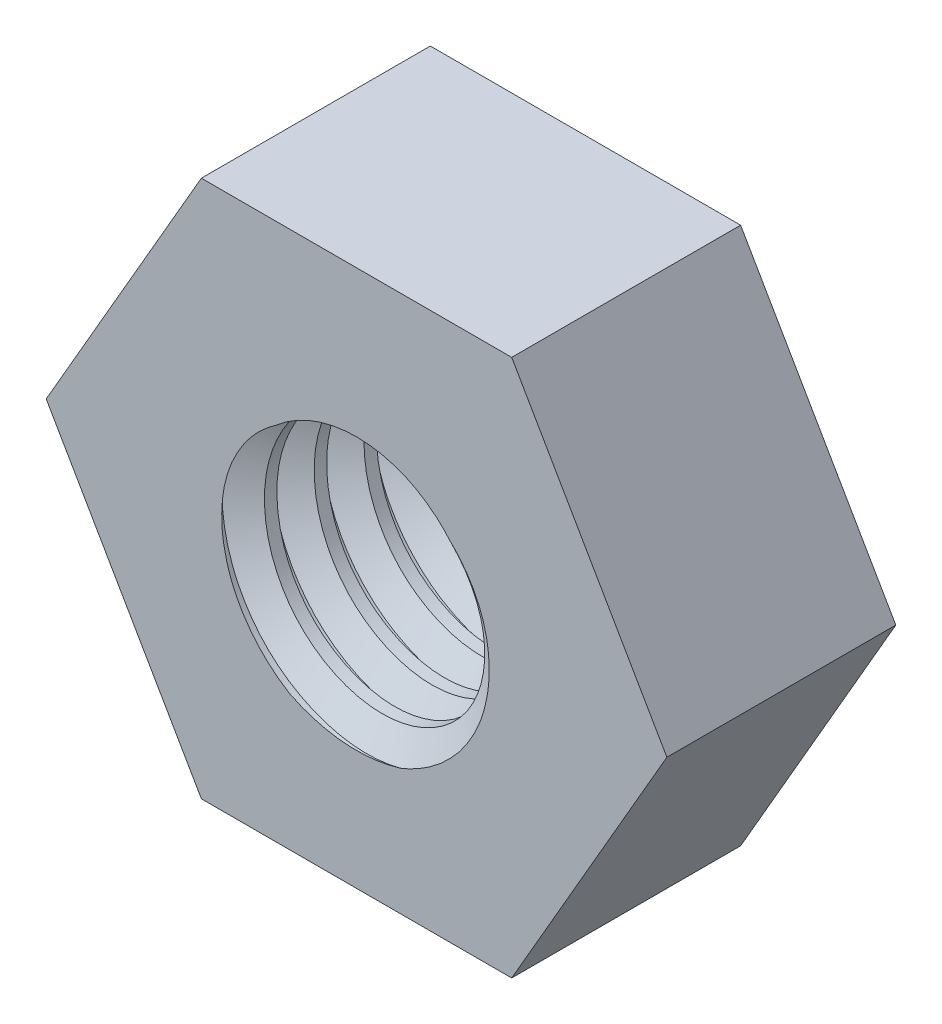
SolidWorks part; units mm, degrees
ref_plane "Plano frontal" through (0, 0, 0) normal (0, 0, 1) x (1, 0, 0)
ref_plane "Plano superior" through (0, 0, 0) normal (0, 1, 0) x (1, 0, 0)
ref_plane "Plano direito" through (0, 0, 0) normal (1, 0, 0) x (0, 0, -1)
sketch "Esboço1" plane through (0, 0, 0) normal (0, 0, 1) x (1, 0, 0)
  line L0 (3.1177, 0) -> (0, 0) construction
  line L1 (3.1177, 0) -> (1.5588, 2.7)
  line L2 (1.5588, 2.7) -> (-1.5588, 2.7)
  line L3 (-1.5588, 2.7) -> (-3.1177, 0)
  line L4 (-3.1177, 0) -> (-1.5588, -2.7)
  line L5 (-1.5588, -2.7) -> (1.5588, -2.7)
  line L6 (1.5588, -2.7) -> (3.1177, 0)
  circle A0 centre (0, 0) radius 2.7 construction
  circle A1 centre (0, 0) radius 1.5
  dimension "D1" = 5.4
  dimension "D2" = 3
extrude "Ressalto-extrusão1" add sketch "Esboço1" along normal blind 5 and the other way blind 5
thread "Rosca1" pitch 0.5 method extrude profile "Perfil da rosca2" start angle 0, offset 0, length 0, pitch 0.5, diameter 3
ref_plane "Plano2" through (-1.5, 0, 5) normal (0, -1, 0) x (-1, 0, 0)
sketch "Perfil da rosca2" plane through (-1.5, 0, 5) normal (0, -1, 0) x (-1, 0, 0)
  line L0 (0, 0) -> (0, 0.5) construction
  line L11 (0, 0) -> (0, 0.4375)
  line L12 (0, 0.4375) -> (-0.2706, 0.2812)
  line L13 (-0.2706, 0.2812) -> (-0.2706, 0.1562)
  line L15 (-0.2706, 0.1562) -> (0, 0)
  line L17 (-0.2706, 0.2187) -> (0, 0.2187) construction
  point P2 (0, 0)
  dimension "Pitch" = 0.5
  dimension "Profile_Angle" = 60
  dimension "Profile_Land" = 0.125
  dimension "Profile_Height" = 0.2706
sketch "Esboço8" plane through (0, 0, 0) normal (0, 1, 0) x (1, 0, 0)
  line L0 (-3.1177, 5) -> (-3.1177, -5) construction
  line L1 (-3.1177, 1.15) -> (3.1177, 1.15)
  line L2 (-3.1177, 1.15) -> (-3.1177, -1.15)
  line L3 (-3.1177, -1.15) -> (3.1177, -1.15)
  line L4 (3.1177, 1.15) -> (3.1177, -1.15)
  line L5 (-3.1177, 1.15) -> (3.1177, -1.15) construction
  line L6 (-3.1177, -1.15) -> (3.1177, 1.15) construction
  line L8 (-3.1177, 7.5) -> (3.1177, 7.5)
  line L9 (-3.1177, 7.5) -> (-3.1177, -7.5)
  line L10 (-3.1177, -7.5) -> (3.1177, -7.5)
  line L11 (3.1177, 7.5) -> (3.1177, -7.5)
  line L12 (-3.1177, 7.5) -> (3.1177, -7.5) construction
  line L13 (-3.1177, -7.5) -> (3.1177, 7.5) construction
  point P4 (0, 0)
  point P13 (0, 0)
  dimension "D1" = 2.3
  dimension "D2" = 15
extrude "Corte-extrusão1" cut sketch "Esboço8" against normal through all both and the other way through all contours L11 L8 L9 L1 | L11 L3 L9 L10 region at (0, 0, -4.325) region at (0, 0, 4.325)
